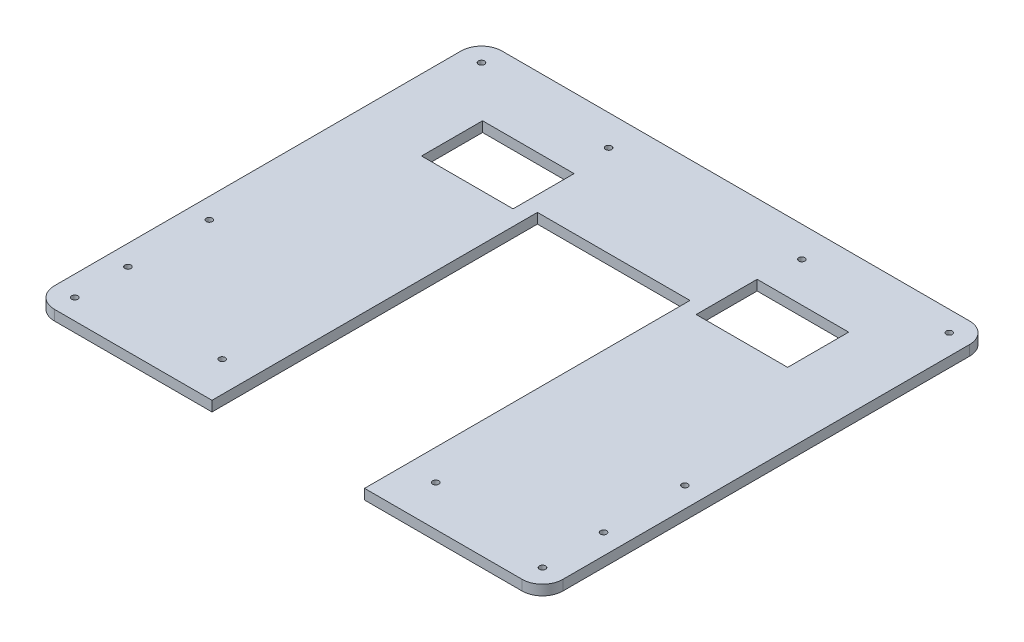
SolidWorks part; units mm, degrees
ref_plane "前视基准面" through (0, 0, 0) normal (0, 0, 1) x (1, 0, 0)
ref_plane "上视基准面" through (0, 0, 0) normal (0, 1, 0) x (1, 0, 0)
ref_plane "右视基准面" through (0, 0, 0) normal (1, 0, 0) x (0, 0, -1)
sketch "草图1" plane through (0, 0, 0) normal (0, 1, 0) x (1, 0, 0)
  line L1 (10, 0) -> (240, 0)
  line L2 (0, -10) -> (0, -210)
  line L3 (10, -220) -> (240, -220)
  line L4 (250, -10) -> (250, -210)
  arc A0 (0, -210) -> (10, -220) centre (10, -210) ccw
  arc A1 (240, -220) -> (250, -210) centre (240, -210) ccw
  arc A2 (240, 0) -> (250, -10) centre (240, -10) cw
  arc A3 (10, 0) -> (0, -10) centre (10, -10) ccw
  point P9 (250, -220)
  point P12 (250, 0)
  point P15 (0, 0)
  dimension "D3" = 10
  dimension "D1" = 250
  dimension "D2" = 220
extrude "凸台-拉伸1" add sketch "草图1" along normal blind 5
sketch "草图2" plane through (0, 0, 0) normal (0, -1, 0) x (1, 0, 0)
  line L0 (239.1778, 11.85) -> (239.1778, 76.15) construction
  line L1 (239.1778, 11.85) -> (239.1778, 76.15)
  line L2 (250, 210) -> (250, 10) construction
  line L3 (239.1778, 76.15) -> (250, 76.15)
  line L4 (239.1778, 76.15) -> (239.1778, 0)
  line L5 (239.1778, 0) -> (250, 0)
  line L6 (250, 76.15) -> (250, 0)
  line L7 (125, 220) -> (125, 0) construction
  line L8 (10, 220) -> (240, 220) construction
  line L9 (240, 0) -> (10, 0) construction
  line L10 (0, 76.15) -> (0, 0)
  line L11 (10.8222, 0) -> (0, 0)
  line L12 (10.8222, 76.15) -> (10.8222, 0)
  line L13 (10.8222, 76.15) -> (0, 76.15)
sketch "草图4" plane through (0, 0, 0) normal (0, -1, 0) x (1, 0, 0)
  line L1 (125, 0) -> (125, 220) construction
  line L2 (240, 0) -> (10, 0) construction
  line L3 (10, 220) -> (240, 220) construction
  line L8 (170, 64.475) -> (170, 34.475)
  line L16 (215, 34.475) -> (170, 34.475)
  line L17 (215, 64.475) -> (215, 34.475)
  line L18 (215, 64.475) -> (170, 64.475)
  line L19 (209.9, 64.475) -> (215, 64.475)
  line L20 (215, 64.475) -> (215, 46.825)
  line L21 (204.1, 64.475) -> (199, 64.475)
  line L22 (209.9, 64.475) -> (215, 64.475)
  line L23 (204.1, 64.475) -> (199, 64.475)
  line L24 (40.1, 64.475) -> (45.9, 64.475)
  line L25 (35, 64.475) -> (35, 46.825)
  line L26 (45.9, 64.475) -> (51, 64.475)
  line L27 (215, 64.475) -> (215, 46.825)
  line L28 (209.9, 64.475) -> (204.1, 64.475)
  line L29 (0, 10) -> (0, 210) construction
  line L30 (40.1, 64.475) -> (35, 64.475)
  line L31 (45.9, 64.475) -> (51, 64.475)
  line L33 (35, 64.475) -> (35, 46.825)
  line L35 (40.1, 64.475) -> (35, 64.475)
  line L38 (35, 64.475) -> (80, 64.475)
  line L39 (35, 64.475) -> (35, 34.475)
  line L120 (35, 34.475) -> (80, 34.475)
  line L121 (80, 64.475) -> (80, 34.475)
  dimension "D3" = 45
  dimension "D4" = 30
  dimension "D1" = 35
extrude "切除-拉伸3" cut sketch "草图4" against normal blind 5 contours L24 L30 L25 L26 | L18 L8 L16 L17 region at (57.5, 0, 49.475)
sketch "草图5" plane through (0, 0, 0) normal (0, -1, 0) x (1, 0, 0)
  line L0 (125, 220) -> (125, 0) construction
  line L1 (10, 220) -> (240, 220) construction
  line L2 (240, 0) -> (10, 0) construction
  line L3 (87.5, 220) -> (162.5, 220) construction
  line L4 (87.5, 220) -> (87.5, 60)
  line L5 (162.5, 220) -> (87.5, 220)
  line L6 (162.5, 220) -> (162.5, 60)
  line L7 (162.5, 60) -> (87.5, 60)
  point P11 (125, 60)
  dimension "D1" = 37.5
  dimension "D2" = 160
extrude "切除-拉伸4" cut sketch "草图5" against normal blind 5
sketch "草图6" plane through (0, 0, 0) normal (0, -1, 0) x (1, 0, 0)
  line L0 (72.5, 220) -> (72.5, 200) construction
  line L1 (10, 220) -> (87.5, 220) construction
  line L2 (72.5, 200) -> (87.5, 200) construction
  line L7 (87.5, 220) -> (87.5, 60) construction
  line L8 (125, 60) -> (125, 181.8158) construction
  line L9 (87.5, 60) -> (162.5, 60) construction
  line L10 (87.5, 60) -> (87.5, 0) construction
  line L11 (240, 0) -> (10, 0) construction
  line L12 (87.5, 20) -> (92.5, 20) construction
  line L13 (92.5, 20) -> (92.5, 0) construction
  line L14 (92.5, 20) -> (107.5, 20) construction
  circle A0 centre (72.5, 200) radius 1.5
  circle A3 centre (177.5, 200) radius 1.5
  dimension "D3" = 3
  dimension "D1" = 20
  dimension "D2" = 15
  dimension "D4" = 5
  dimension "D5" = 20
  dimension "D6" = 15
extrude "切除-拉伸5" cut sketch "草图6" against normal up to next contours A0 | A3
sketch "草图7" plane through (0, 0, 0) normal (0, -1, 0) x (1, 0, 0)
  line L0 (17, 15) -> (17, 73) construction
  line L1 (25, 29) -> (25, 59) construction
  line L2 (17, 44) -> (25, 44) construction
  line L3 (240, 0) -> (10, 0) construction
  line L5 (125, 60) -> (125, 0) construction
  line L6 (87.5, 60) -> (162.5, 60) construction
  line L8 (233, 44) -> (225, 44) construction
  line L9 (225, 29) -> (225, 59) construction
  line L10 (233, 15) -> (233, 73) construction
  line L11 (0, 10) -> (0, 210) construction
  circle A0 centre (17, 15) radius 1.6
  circle A1 centre (25, 29) radius 1.6
  circle A2 centre (25, 59) radius 1.6
  circle A3 centre (17, 73) radius 1.6
  circle A4 centre (233, 73) radius 1.6
  circle A5 centre (225, 59) radius 1.6
  circle A6 centre (225, 29) radius 1.6
  circle A7 centre (233, 15) radius 1.6
  dimension "D1" = 8
  dimension "D2" = 58
  dimension "D3" = 30
  dimension "D4" = 58
  dimension "D5" = 17
  dimension "D6" = 15
sketch "草图8" plane through (0, 0, 0) normal (0, -1, 0) x (1, 0, 0)
  line L0 (250, 170) -> (235, 170) construction
  line L1 (250, 210) -> (250, 10) construction
  line L2 (235, 170) -> (235, 220) construction
  line L3 (162.5, 220) -> (240, 220) construction
  line L4 (235, 170) -> (235, 100) construction
  line L5 (235, 100) -> (250, 100) construction
  line L6 (125, 60) -> (125, 122.441) construction
  line L7 (87.5, 60) -> (162.5, 60) construction
  line L8 (15, 170) -> (15, 100) construction
  circle A0 centre (235, 170) radius 1.5
  circle A1 centre (235, 100) radius 1.5
  circle A2 centre (15, 100) radius 1.5
  circle A3 centre (15, 170) radius 1.5
  dimension "D4" = 3
  dimension "D5" = 3
  dimension "D1" = 15
  dimension "D2" = 50
  dimension "D3" = 70
sketch "草图9" plane through (0, 0, 0) normal (0, -1, 0) x (1, 0, 0)
  line L0 (87.5, 60) -> (87.5, 0) construction
  line L1 (240, 0) -> (10, 0) construction
  line L2 (87.5, 0) -> (87.5, 15) construction
  line L3 (87.5, 15) -> (77.5, 15) construction
  line L4 (10, 220) -> (10, 210) construction
  line L5 (125, 60) -> (125, 0) construction
  line L6 (87.5, 60) -> (162.5, 60) construction
  circle A0 centre (77.5, 15) radius 1.5
  circle A1 centre (10, 210) radius 1.5
  circle A2 centre (240, 210) radius 1.5
  circle A3 centre (172.5, 15) radius 1.5
  dimension "D3" = 3
  dimension "D4" = 3
  dimension "D1" = 15
  dimension "D2" = 10
extrude "切除-拉伸9" cut sketch "草图9" against normal up to next
sketch "草图10" plane through (0, 0, 0) normal (0, -1, 0) x (1, 0, 0)
  line L0 (125, 60) -> (125, 0) construction
  line L1 (0, 0) -> (8, 0)
  line L2 (0, 0) -> (0, 85)
  line L3 (0, 85) -> (8, 85)
  line L4 (8, 0) -> (8, 85)
  line L5 (87.5, 60) -> (162.5, 60) construction
  line L6 (240, 0) -> (10, 0) construction
  line L7 (242, 0) -> (242, 85)
  line L8 (250, 85) -> (242, 85)
  line L9 (250, 0) -> (250, 85)
  line L10 (250, 0) -> (242, 0)
  dimension "D1" = 8
  dimension "D2" = 85
sketch "草图11" plane through (0, 0, 0) normal (0, -1, 0) x (1, 0, 0)
  circle A0 centre (240, 180) radius 1.5 construction
  circle A1 centre (240, 180) radius 1.5
  circle A2 centre (240, 140) radius 1.5 construction
  circle A3 centre (240, 140) radius 1.5
  circle A4 centre (10, 143.8355) radius 1.5 construction
  circle A5 centre (10, 143.8355) radius 1.5
  circle A6 centre (10, 183.8355) radius 1.5 construction
  circle A7 centre (10, 183.8355) radius 1.5
extrude "切除-拉伸10" cut sketch "草图11" against normal up to surface (5 mm away) up to face at (172.5, 5, 16.5)
sketch "草图12" plane through (0, 5, 0) normal (0, 1, 0) x (1, 0, 0)
  line L0 (10, 0) -> (10, -10) construction
  line L1 (125, -60) -> (125, 39.1783) construction
  line L2 (87.5, -60) -> (162.5, -60) construction
  circle A0 centre (10, -10) radius 1.5
  circle A1 centre (240, -10) radius 1.5
  dimension "D1" = 3
extrude "切除-拉伸11" cut sketch "草图12" against normal blind 10
